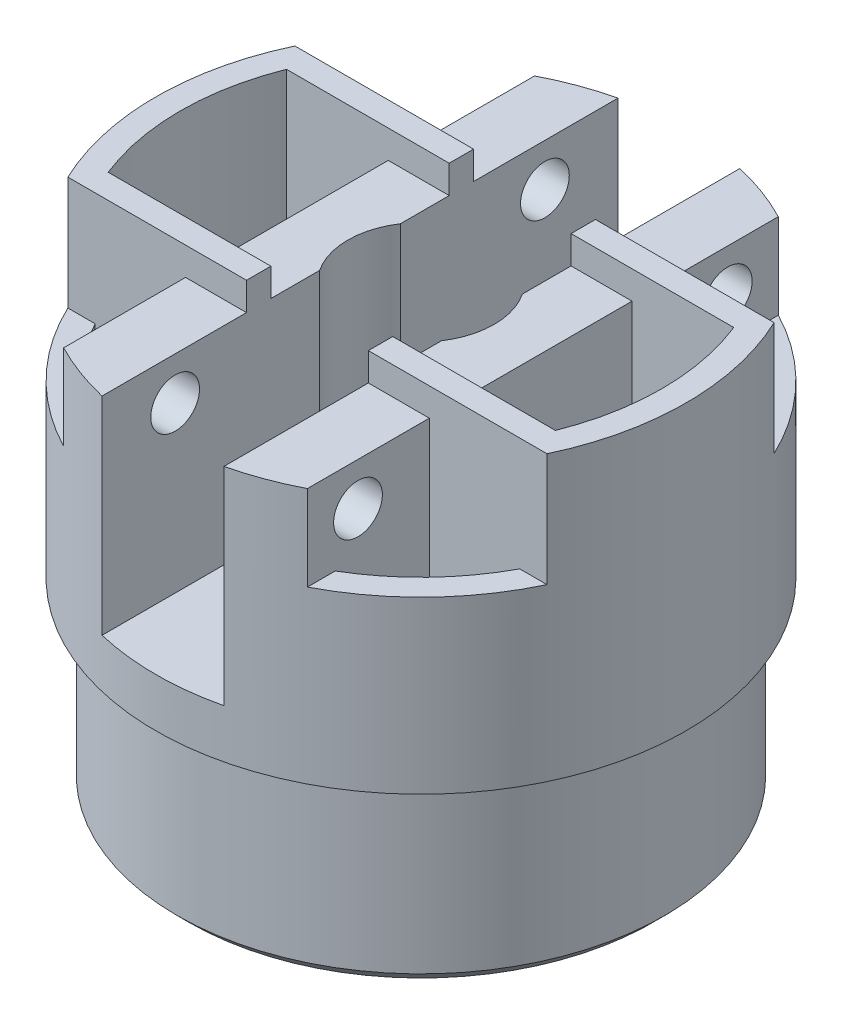
SolidWorks part; units mm, degrees
material "ABS"
ref_plane "Front Plane" through (0, 0, 0) normal (0, 0, 1) x (1, 0, 0)
ref_plane "Top Plane" through (0, 0, 0) normal (0, 1, 0) x (1, 0, 0)
ref_plane "Right Plane" through (0, 0, 0) normal (1, 0, 0) x (0, 0, -1)
sketch "Sketch1" plane through (0, 0, 0) normal (0, 1, 0) x (1, 0, 0)
  line L0 (-6.35, 26.8827) -> (-6.35, 0)
  line L2 (6.35, 0) -> (6.35, 26.8827)
  line L3 (0, 0) -> (0, 27.6225) construction
  line L5 (12.7, 24.5298) -> (12.7, 0)
  line L7 (-12.7, 24.5298) -> (-12.7, 0)
  line L8 (27.6225, 0) -> (-27.6225, 0)
  line L9 (12.7, 11.8298) -> (24.9611, 11.8298)
  line L10 (27.6225, 0) -> (25.0825, 0)
  line L11 (-25.0825, 0) -> (-27.6225, 0)
  line L12 (12.7, 9.2898) -> (23.2987, 9.2898)
  line L13 (-12.7, 9.2898) -> (-23.2987, 9.2898)
  line L14 (-12.7, 11.8298) -> (-24.9611, 11.8298)
  circle A0 centre (0, 0) radius 27.6225 construction
  circle A1 centre (0, 0) radius 25.0825 construction
  arc A2 (-27.6225, 0) -> (27.6225, 0) centre (0, 0) cw
  arc A3 (-25.0825, 0) -> (25.0825, 0) centre (0, 0) cw
  dimension "D1" = 55.245
  dimension "D2" = 2.54
  dimension "D3" = 12.7
  dimension "D5" = 2.54
  dimension "D6" = 6.35
  dimension "D7" = 12.7
extrude "hinge" add sketch "Sketch1" along normal blind 8.89
sketch "Sketch2" plane through (12.7, 0, 0) normal (1, 0, 0) x (0, 0, -1)
  line L0 (19.2627, 8.89) -> (19.2627, 4.445) construction
  line L3 (24.5298, 8.89) -> (11.8298, 8.89) construction
  circle A0 centre (19.2627, 4.445) radius 2.54
  dimension "D2" = 5.08
  dimension "D1" = 7.62
  dimension "D3" = 4.445
extrude "hinge_holes" cut sketch "Sketch2" against normal through all
sketch "Sketch5" plane through (0, 0, 0) normal (0, -1, 0) x (1, 0, 0)
  line L0 (-6.35, -26.8827) -> (-6.35, 0) construction
  line L1 (27.6225, 0) -> (25.0825, 0) construction
  line L2 (6.35, 0) -> (6.35, -26.8827) construction
  line L3 (-27.6225, 0) -> (-25.0825, 0)
  line L4 (-6.35, -24.2654) -> (-6.35, -26.8827)
  line L5 (25.0825, 0) -> (27.6225, 0)
  line L6 (6.35, -24.2654) -> (6.35, -26.8827)
  arc A4 (-27.6225, 0) -> (-6.35, -26.8827) centre (0, 0) ccw
  arc A5 (27.6225, 0) -> (6.35, -26.8827) centre (0, 0) cw
  arc A6 (24.9611, -11.8298) -> (27.6225, 0) centre (0, 0) ccw construction
  arc A7 (6.35, -26.8827) -> (12.7, -24.5298) centre (0, 0) ccw construction
  arc A8 (-25.0825, 0) -> (-6.35, -24.2654) centre (0, 0) ccw
  arc A9 (25.0825, 0) -> (6.35, -24.2654) centre (0, 0) cw
extrude "body" add sketch "Sketch5" along normal blind 12.7
sketch "Sketch6" plane through (0, -12.7, 0) normal (0, -1, 0) x (1, 0, 0)
  line L0 (27.6225, 0) -> (25.0825, 0) construction
  line L1 (27.6225, 0) -> (-27.6225, 0) construction
  line L2 (3.81, 0) -> (13.97, 0)
  line L4 (-3.81, 0) -> (-27.6225, 0) construction
  line L5 (21.59, 0) -> (27.6225, 0)
  line L6 (0, 0) -> (0, -27.6225) construction
  line L7 (-21.59, 0) -> (-27.6225, 0)
  line L8 (-3.81, 0) -> (-13.97, 0)
  arc A0 (-27.6225, 0) -> (27.6225, 0) centre (0, 0) ccw
  arc A2 (-3.81, 0) -> (3.81, 0) centre (0, 0) ccw
  arc A3 (13.97, 0) -> (21.59, 0) centre (17.78, 0) ccw
  arc A4 (-13.97, 0) -> (-21.59, 0) centre (-17.78, 0) cw
  dimension "D1" = 3.81
  dimension "D3" = 17.78
  dimension "D2" = 3.81
extrude "bottom_plate" add sketch "Sketch6" along normal blind 5.08
sketch "Sketch7" plane through (0, -17.78, 0) normal (0, -1, 0) x (1, 0, 0)
  line L1 (-25.4, 0) -> (25.4, 0)
  line L2 (21.59, 0) -> (27.6225, 0) construction
  arc A1 (-27.6225, 0) -> (27.6225, 0) centre (0, 0) ccw construction
  arc A2 (-25.4, 0) -> (25.4, 0) centre (0, 0) ccw
  arc A4 (-22.86, 0) -> (22.86, 0) centre (0, 0) ccw
  point P13 (0, 0)
  dimension "D1" = 2.2225
  dimension "D2" = 2.54
extrude "tube_connection" add sketch "Sketch7" along normal blind 19.05
sketch "Sketch10" plane through (0, 8.89, 0) normal (0, 1, 0) x (1, 0, 0)
  line L0 (-25.0825, 0) -> (-27.6225, 0) construction
  line L1 (-23.2987, 9.2898) -> (-6.35, 9.2898)
  line L2 (-6.35, 26.8827) -> (-6.35, 0) construction
  line L3 (-6.35, 9.2898) -> (-6.35, 11.8298)
  line L4 (-6.35, 11.8298) -> (-24.9611, 11.8298)
  line L5 (-27.6225, 0) -> (-25.0825, 0)
  line L6 (0, 27.6225) -> (0, 0) construction
  line L7 (6.35, 11.8298) -> (24.9611, 11.8298)
  line L8 (6.35, 9.2898) -> (6.35, 11.8298)
  line L9 (23.2987, 9.2898) -> (6.35, 9.2898)
  line L10 (27.6225, 0) -> (25.0825, 0)
  arc A0 (-24.9611, 11.8298) -> (-27.6225, 0) centre (0, 0) ccw
  arc A1 (-23.2987, 9.2898) -> (-25.0825, 0) centre (0, 0) ccw
  arc A2 (-23.2987, 9.2898) -> (-25.0825, 0) centre (0, 0) ccw construction
  arc A3 (6.35, 26.8827) -> (-6.35, 26.8827) centre (0, 0) ccw construction
  arc A4 (24.9611, 11.8298) -> (27.6225, 0) centre (0, 0) cw
  arc A5 (23.2987, 9.2898) -> (25.0825, 0) centre (0, 0) cw
extrude "backstop" add sketch "Sketch10" along normal blind 2.921
mirror "Mirror1" about plane through (0, 8.89, 0) normal (0, 0, 1) of "backstop", "body", "bottom_plate", "hinge", "tube_connection", "hinge_holes"
sketch "Sketch12" plane through (0, 0, 0) normal (0, -1, 0) x (1, 0, 0)
  line L8 (-6.35, -24.2654) -> (-6.35, 24.2654)
  line L9 (-12.7, 21.6297) -> (-12.7, 11.8298)
  line L10 (-12.7, 11.8298) -> (-22.1176, 11.8298)
  line L11 (-23.2987, 9.2898) -> (-12.7, 9.2898)
  line L12 (-12.7, 9.2898) -> (-12.7, -9.2898)
  line L13 (-12.7, -9.2898) -> (-23.2987, -9.2898)
  line L14 (-22.1176, -11.8298) -> (-12.7, -11.8298)
  line L15 (-12.7, -11.8298) -> (-12.7, -21.6297)
  line L16 (-6.35, -24.2654) -> (-6.35, 24.2654)
  line L17 (-12.7, 21.6297) -> (-12.7, 11.8298)
  line L18 (-12.7, 11.8298) -> (-22.1176, 11.8298)
  line L19 (-23.2987, 9.2898) -> (-12.7, 9.2898)
  line L20 (-12.7, 9.2898) -> (-12.7, -9.2898)
  line L21 (-12.7, -9.2898) -> (-23.2987, -9.2898)
  line L22 (-22.1176, -11.8298) -> (-12.7, -11.8298)
  line L23 (-12.7, -11.8298) -> (-12.7, -21.6297)
  line L24 (12.7, 9.2898) -> (23.2987, 9.2898)
  line L25 (22.1176, 11.8298) -> (12.7, 11.8298)
  line L26 (12.7, 11.8298) -> (12.7, 21.6297)
  line L27 (6.35, 24.2654) -> (6.35, -24.2654)
  line L28 (12.7, -21.6297) -> (12.7, -11.8298)
  line L29 (12.7, -11.8298) -> (22.1176, -11.8298)
  line L30 (23.2987, -9.2898) -> (12.7, -9.2898)
  line L31 (12.7, -9.2898) -> (12.7, 9.2898)
  line L32 (12.7, 9.2898) -> (23.2987, 9.2898)
  line L33 (22.1176, 11.8298) -> (12.7, 11.8298)
  line L34 (12.7, 11.8298) -> (12.7, 21.6297)
  line L35 (6.35, 24.2654) -> (6.35, -24.2654)
  line L36 (12.7, -21.6297) -> (12.7, -11.8298)
  line L37 (12.7, -11.8298) -> (22.1176, -11.8298)
  line L38 (23.2987, -9.2898) -> (12.7, -9.2898)
  line L39 (12.7, -9.2898) -> (12.7, 9.2898)
  arc A4 (-6.35, 24.2654) -> (-12.7, 21.6297) centre (0, 0) ccw
  arc A5 (-22.1176, 11.8298) -> (-23.2987, 9.2898) centre (0, 0) ccw
  arc A6 (-23.2987, -9.2898) -> (-22.1176, -11.8298) centre (0, 0) ccw
  arc A7 (-12.7, -21.6297) -> (-6.35, -24.2654) centre (0, 0) ccw
  arc A8 (-6.35, 24.2654) -> (-12.7, 21.6297) centre (0, 0) ccw
  arc A9 (-22.1176, 11.8298) -> (-23.2987, 9.2898) centre (0, 0) ccw
  arc A10 (-23.2987, -9.2898) -> (-22.1176, -11.8298) centre (0, 0) ccw
  arc A11 (-12.7, -21.6297) -> (-6.35, -24.2654) centre (0, 0) ccw
  arc A12 (23.2987, 9.2898) -> (22.1176, 11.8298) centre (0, 0) ccw
  arc A13 (12.7, 21.6297) -> (6.35, 24.2654) centre (0, 0) ccw
  arc A14 (6.35, -24.2654) -> (12.7, -21.6297) centre (0, 0) ccw
  arc A15 (22.1176, -11.8298) -> (23.2987, -9.2898) centre (0, 0) ccw
  arc A16 (23.2987, 9.2898) -> (22.1176, 11.8298) centre (0, 0) ccw
  arc A17 (12.7, 21.6297) -> (6.35, 24.2654) centre (0, 0) ccw
  arc A18 (6.35, -24.2654) -> (12.7, -21.6297) centre (0, 0) ccw
  arc A19 (22.1176, -11.8298) -> (23.2987, -9.2898) centre (0, 0) ccw
  dimension "D1" = 0
  dimension "D2" = 0
extrude "connect_to_base" add sketch "Sketch12" along normal up to surface (12.7 mm away) up to face at (0, -12.7, 0)
sketch "Sketch13" plane through (0, -12.7, 0) normal (0, 1, 0) x (1, 0, 0)
  circle A0 centre (0, 0) radius 7.62
  dimension "D1" = 15.24
extrude "bolt_access" cut sketch "Sketch13" along normal up to surface (21.59 mm away) up to face at (-9.525, 8.89, 0)
chamfer "bottom_chamfer" distance 1.27 angle 45 1 edges at (0, -36.83, -25.4)
